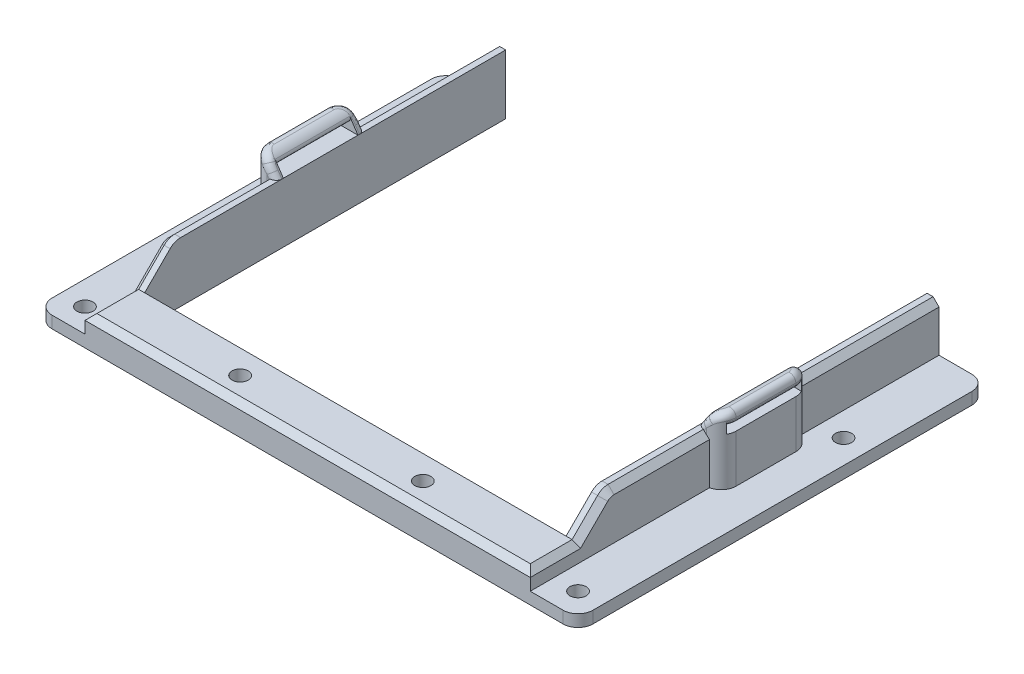
SolidWorks part; units mm, degrees
ref_plane "Front Plane" through (0, 0, 0) normal (0, 0, 1) x (1, 0, 0)
ref_plane "Top Plane" through (0, 0, 0) normal (0, 1, 0) x (1, 0, 0)
ref_plane "Right Plane" through (0, 0, 0) normal (1, 0, 0) x (0, 0, -1)
sketch "Sketch1" plane through (0, 0, 0) normal (0, 1, 0) x (1, 0, 0)
  line L0 (204.7875, -25.4) -> (204.7875, 148.59)
  line L1 (0, 0) -> (179.3875, 0)
  line L2 (0, 0) -> (0, 148.59)
  line L3 (-25.4, -25.4) -> (204.7875, -25.4)
  line L4 (179.3875, 0) -> (179.3875, 148.59)
  line L5 (-25.4, -25.4) -> (-25.4, 148.59)
  line L6 (204.7875, 148.59) -> (179.3875, 148.59)
  line L7 (0, 148.59) -> (-25.4, 148.59)
  dimension "D1" = 179.3875
  dimension "D2" = 148.59
  dimension "D3" = 148.59
  dimension "D4" = 25.4
extrude "Boss-Extrude1" add sketch "Sketch1" along normal blind 5.08
sketch "Sketch2" plane through (0, 5.08, 0) normal (0, 1, 0) x (1, 0, 0)
  line L6 (184.4675, 148.59) -> (179.3875, 148.59)
  line L7 (179.3875, 148.59) -> (179.3875, 0)
  line L8 (179.3875, 0) -> (0, 0)
  line L9 (184.4675, 148.59) -> (184.4675, -5.08)
  line L10 (184.4675, -5.08) -> (-5.08, -5.08)
  line L11 (-5.08, -5.08) -> (-5.08, 148.59)
  line L12 (184.4675, 148.59) -> (184.4675, -5.08)
  line L13 (184.4675, -5.08) -> (-5.08, -5.08)
  line L14 (-5.08, -5.08) -> (-5.08, 148.59)
  line L15 (0, 0) -> (0, 148.59)
  line L16 (0, 148.59) -> (-5.08, 148.59)
  dimension "D1" = 5.08
extrude "Boss-Extrude2" add sketch "Sketch2" along normal blind 20.32
fillet "Fillet1" radius 6.35 4 edges at (204.7875, 2.54, -148.59) (204.7875, 2.54, 25.4) (-25.4, 2.54, 25.4) (-25.4, 2.54, -148.59)
sketch "Sketch3" plane through (0, 5.08, 0) normal (0, 1, 0) x (1, 0, 0)
  line L0 (-5.08, 148.59) -> (-5.08, -5.08) construction
  line L1 (-5.08, 88.9) -> (-10.16, 88.9)
  line L2 (-5.08, 88.9) -> (-5.08, 50.8)
  line L3 (-5.08, 50.8) -> (-10.16, 50.8)
  line L4 (-10.16, 88.9) -> (-10.16, 50.8)
  line L5 (184.4675, -5.08) -> (184.4675, 148.59) construction
  line L6 (184.4675, 50.8) -> (189.5475, 50.8)
  line L7 (184.4675, 50.8) -> (184.4675, 88.9)
  line L8 (184.4675, 88.9) -> (189.5475, 88.9)
  line L9 (189.5475, 50.8) -> (189.5475, 88.9)
  line L10 (-19.05, -25.4) -> (198.4375, -25.4) construction
  dimension "D1" = 38.1
  dimension "D2" = 38.1
  dimension "D3" = 76.2
  dimension "D4" = 76.2
  dimension "D5" = 5.08
  dimension "D6" = 5.08
extrude "Boss-Extrude3" add sketch "Sketch3" along normal blind 27.94
sketch "Sketch4" plane through (0, 0, -88.9) normal (0, 0, -1) x (-1, 0, 0)
  line L0 (-184.4675, 33.02) -> (-179.3875, 25.4)
  line L1 (-179.3875, 25.4) -> (-184.4675, 25.4)
  line L2 (-184.4675, 25.4) -> (-184.4675, 33.02)
  line L3 (5.08, 33.02) -> (0, 25.4)
  line L4 (5.08, 25.4) -> (-184.4675, 25.4) construction
  line L5 (-179.3875, 25.4) -> (0, 25.4) construction
  line L6 (0, 25.4) -> (5.08, 25.4)
  line L7 (5.08, 25.4) -> (5.08, 33.02)
extrude "Boss-Extrude4" add sketch "Sketch4" against normal up to surface (38.1 mm away) up to face at (-7.112, 20.32, -50.8)
sketch "Sketch5" plane through (189.5475, 0, 0) normal (1, 0, 0) x (0, 0, -1)
  line L0 (-5.08, 25.4) -> (50.8, 25.4) construction
  line L1 (53.975, 25.4) -> (85.725, 25.4)
  line L2 (53.975, 25.4) -> (53.975, 28.575)
  line L3 (53.975, 28.575) -> (85.725, 28.575)
  line L4 (85.725, 25.4) -> (85.725, 28.575)
  line L5 (50.8, 33.02) -> (50.8, 5.08) construction
  dimension "D1" = 0
  dimension "D2" = 3.175
  dimension "D3" = 31.75
  dimension "D4" = 3.175
extrude "Cut-Extrude1" cut sketch "Sketch5" against normal through all both and the other way through all
sketch "Sketch6" plane through (0, 0, 0) normal (0, 0, -1) x (-1, 0, 0)
  line L0 (0, 25.4) -> (0, 0) construction
  line L1 (-179.3875, 25.4) -> (0, 25.4)
  line L2 (-179.3875, 25.4) -> (-179.3875, 12.7)
  line L3 (-179.3875, 12.7) -> (0, 12.7)
  line L4 (0, 25.4) -> (0, 12.7)
extrude "Cut-Extrude2" cut sketch "Sketch6" against normal through all
sketch "Sketch8" plane through (179.3875, 0, 0) normal (-1, 0, 0) x (0, 0, 1)
  line L0 (5.08, 12.7) -> (0, 7.62)
  line L1 (0, 7.62) -> (0, 12.7)
  line L2 (0, 12.7) -> (5.08, 12.7)
extrude "Cut-Extrude3" cut sketch "Sketch8" along normal up to surface (179.3875 mm away) up to face at (0, 17.78, -56.642)
sketch "Sketch9" plane through (184.4675, 0, 0) normal (1, 0, 0) x (0, 0, -1)
  line L0 (-5.08, 12.7) -> (7.62, 25.4)
  line L1 (-5.08, 25.4) -> (50.8, 25.4) construction
  line L2 (7.62, 25.4) -> (-5.08, 25.4)
  line L3 (-5.08, 25.4) -> (-5.08, 12.7)
  dimension "D1" = 45
extrude "Cut-Extrude4" cut sketch "Sketch9" against normal through all both and the other way through all
fillet "Fillet3" radius 6.35 1 edges at (89.6938, 7.62, 0)
fillet "Fillet4" radius 6.35 8 edges at (-10.16, 19.05, -88.9) (-10.16, 19.05, -50.8) (189.5475, 19.05, -88.9) (189.5475, 19.05, -50.8) (-5.08, 33.02, -69.85) (184.4675, 33.02, -69.85) (-2.54, 25.4, -7.62) (181.9275, 25.4, -7.62)
fillet "Fillet5" radius 1.27 8 edges at (-2.1167, 28.575, -69.85) (181.5042, 28.575, -69.85) (189.3311, 28.575, -55.5065) (189.3311, 28.575, -84.1935) (-9.9436, 28.575, -84.1935) (-9.9436, 28.575, -55.5065) (189.5475, 28.575, -69.85) (-10.16, 28.575, -69.85)
sketch "Sketch10" plane through (-5.08, 0, 0) normal (-1, 0, 0) x (0, 0, 1)
  line L1 (5.08, 12.7) -> (25.4, 12.7)
  line L2 (5.08, 12.7) -> (5.08, 5.08)
  line L3 (5.08, 5.08) -> (25.4, 5.08)
  line L4 (25.4, 12.7) -> (25.4, 5.08)
extrude "Boss-Extrude5" add sketch "Sketch10" against normal up to surface (189.5475 mm away) up to face at (184.4675, 16.2744, -13.253)
chamfer "Chamfer1" distance 2.54 angle 45 1 edges at (89.6938, 12.7, 25.4)
chamfer "Chamfer2" distance 2.54 angle 45 10 edges at (184.4675, 25.4, -118.6809) (184.4675, 25.4, -30.5893) (184.4675, 24.9166, -7.8202) (184.4675, 18.1201, -0.3401) (184.4675, 12.7, 13.97) (-5.08, 25.4, -118.6809) (-5.08, 12.7, 13.97) (-5.08, 25.4, -30.5893) (-5.08, 24.9166, -7.8202) (-5.08, 18.1201, -0.3401)
fillet "Fillet8" radius 2.54 14 edges at (-1.5974, 27.7962, -88.9) (-3.4871, 30.5955, -88.9) (-5.1252, 32.0624, -88.7623) (-9.7247, 33.02, -84.8606) (-1.5974, 27.7962, -50.8) (-3.4871, 30.5955, -50.8) (-5.1252, 32.0624, -50.9377) (180.9849, 27.7962, -50.8) (182.8746, 30.5955, -50.8) (184.5127, 32.0624, -50.9377) (189.1122, 33.02, -54.8394) (180.9849, 27.7962, -88.9) (182.8746, 30.5955, -88.9) (184.5127, 32.0624, -88.7623)
sketch "Sketch11" plane through (0, 5.08, 0) normal (0, 1, 0) x (1, 0, 0)
  line L0 (-25.4, 142.24) -> (-25.4, -19.05) construction
  line L1 (204.7875, -19.05) -> (204.7875, 142.24) construction
  line L2 (-5.08, 148.59) -> (-19.05, 148.59) construction
  line L3 (198.4375, 148.59) -> (179.3875, 148.59) construction
  line L4 (198.4375, 148.59) -> (184.4675, 148.59) construction
  line L5 (184.4675, -25.4) -> (198.4375, -25.4) construction
  line L6 (-19.05, -25.4) -> (-5.08, -25.4) construction
  line L7 (184.4675, -25.4) -> (-5.08, -25.4) construction
  circle A0 centre (-15.24, -15.24) radius 3.429
  circle A1 centre (194.6275, -15.24) radius 3.429
  circle A2 centre (194.6275, 97.79) radius 3.429
  circle A3 centre (-15.24, 97.79) radius 3.429
  circle A4 centre (50.8, -15.24) radius 3.429
  circle A5 centre (128.5875, -15.24) radius 3.429
  point P14 (188.9125, 148.59)
  dimension "D1" = 6.858
  dimension "D2" = 6.858
  dimension "D3" = 6.858
  dimension "D4" = 6.858
  dimension "D15" = 6.858
  dimension "D16" = 6.858
  dimension "D5" = 10.16
  dimension "D6" = 10.16
  dimension "D7" = 10.16
  dimension "D8" = 10.16
  dimension "D9" = 50.8
  dimension "D10" = 50.8
  dimension "D11" = 10.16
  dimension "D12" = 10.16
  dimension "D13" = 10.16
  dimension "D14" = 10.16
  dimension "D17" = 76.2
  dimension "D18" = 76.2
extrude "Cut-Extrude5" cut sketch "Sketch11" against normal through all both and the other way through all
